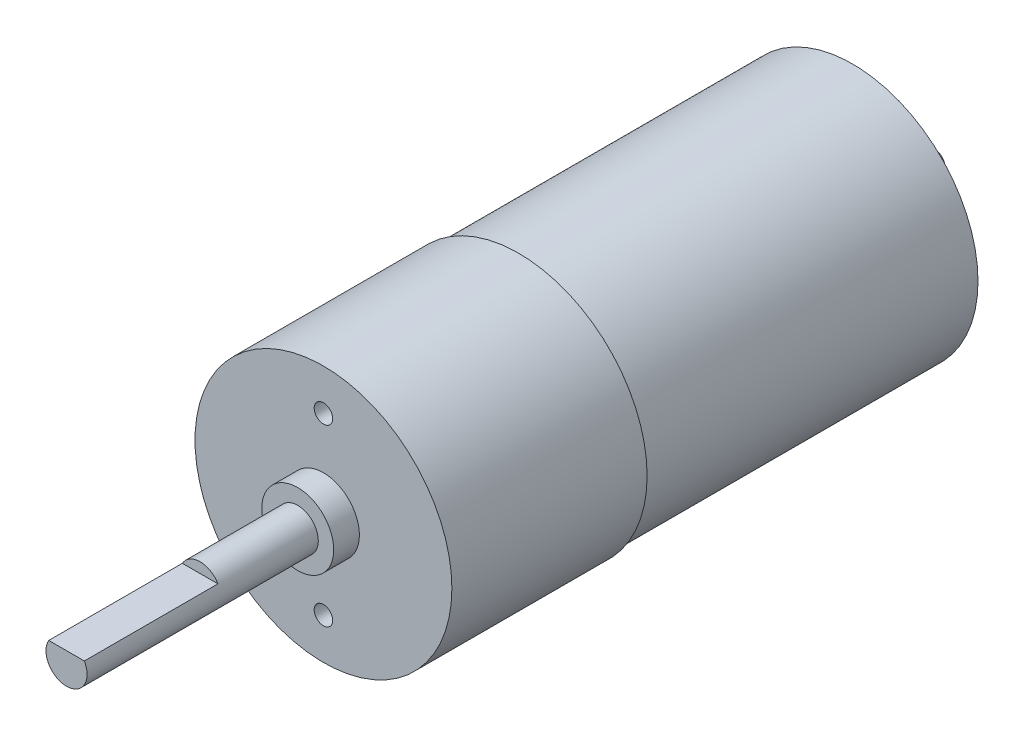
SolidWorks part; units mm, degrees
ref_plane "Front Plane" through (0, 0, 0) normal (0, 0, 1) x (1, 0, 0)
ref_plane "Top Plane" through (0, 0, 0) normal (0, 1, 0) x (1, 0, 0)
ref_plane "Right Plane" through (0, 0, 0) normal (1, 0, 0) x (0, 0, -1)
sketch "스케치1" plane through (0, 0, 0) normal (0, 0, 1) x (1, 0, 0)
  circle A0 centre (0, 0) radius 12.5
extrude "보스-돌출1" add sketch "스케치1" along normal blind 19
sketch "스케치2" plane through (0, 0, 19) normal (0, 0, 1) x (1, 0, 0)
  circle A0 centre (0, 0) radius 3.5
extrude "보스-돌출2" add sketch "스케치2" along normal blind 2.5
sketch "스케치3" plane through (0, 0, 21.5) normal (0, 0, 1) x (1, 0, 0)
  circle A0 centre (0, 0) radius 2
extrude "보스-돌출3" add sketch "스케치3" along normal blind 22.5
sketch "스케치4" plane through (0, 0, 44) normal (0, 0, 1) x (1, 0, 0)
  line L0 (0, 0) -> (50000, 0) construction
  line L1 (-2.3599, 1) -> (49997.6401, 1) construction
  line L3 (3.3297, 1) -> (-3.2328, 1)
  line L4 (3.3297, 1) -> (3.3297, 2.1821)
  line L5 (3.3297, 2.1821) -> (-3.2328, 2.1821)
  line L6 (-3.2328, 1) -> (-3.2328, 2.1821)
  dimension "D1" = 1
extrude "컷-돌출1" cut sketch "스케치4" against normal blind 13
sketch "스케치5" plane through (0, 0, 0) normal (0, 0, -1) x (-1, 0, 0)
  circle A0 centre (0, 0) radius 12.2
extrude "보스-돌출5" add sketch "스케치5" along normal blind 32.5
sketch "스케치6" plane through (0, 0, -32.5) normal (0, 0, -1) x (-1, 0, 0)
  circle A0 centre (0, 0) radius 3.5
extrude "보스-돌출6" add sketch "스케치6" along normal blind 3
sketch "스케치7" plane through (0, 0, -35.5) normal (0, 0, -1) x (-1, 0, 0)
  circle A0 centre (0, 0) radius 1
extrude "보스-돌출7" add sketch "스케치7" along normal blind 5
sketch "스케치8" plane through (0, 0, 19) normal (0, 0, 1) x (1, 0, 0)
  line L0 (0, 0.6304) -> (0, 50000.6304) construction
  circle A0 centre (0, 0) radius 8.5 construction
  circle A1 centre (0, 8.5) radius 0.9
  circle A2 centre (0, -8.5) radius 0.9
extrude "컷-돌출2" cut sketch "스케치8" against normal blind 5
